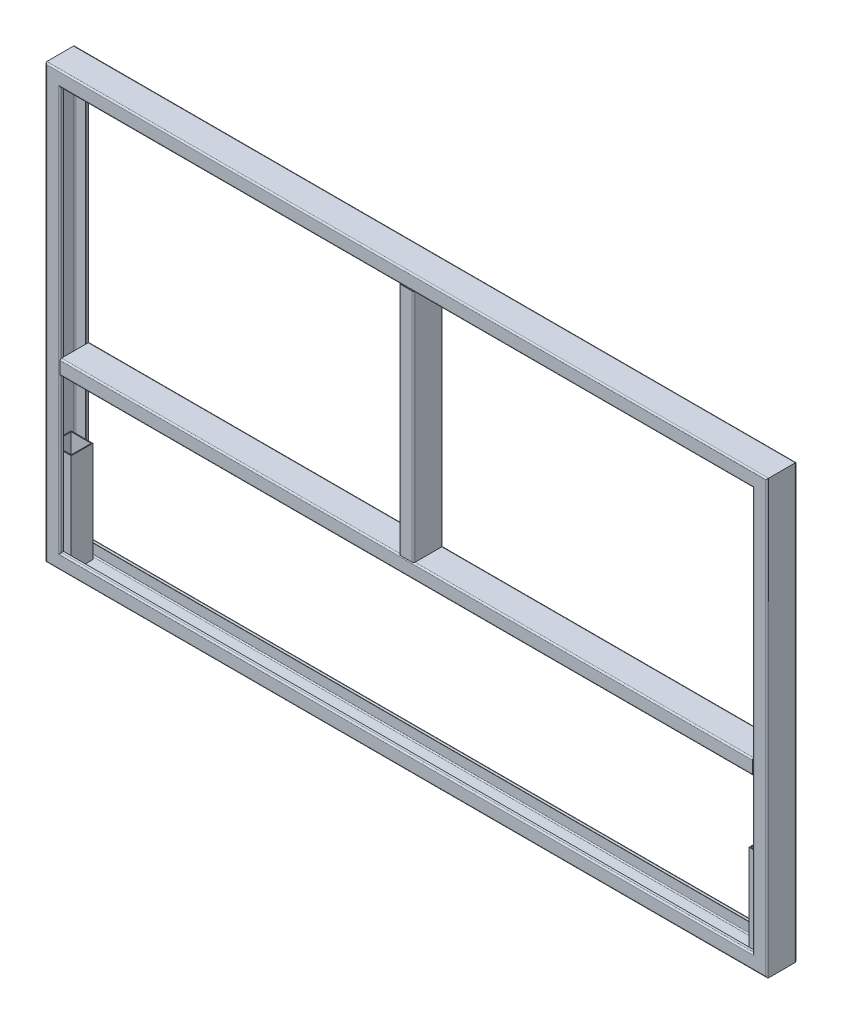
SolidWorks part; units mm, degrees
material "Plain Carbon Steel"
ref_plane "Front Plane" through (0, 0, 0) normal (0, 0, 1) x (1, 0, 0)
ref_plane "Top Plane" through (0, 0, 0) normal (0, 1, 0) x (1, 0, 0)
ref_plane "Right Plane" through (0, 0, 0) normal (1, 0, 0) x (0, 0, -1)
sketch "Sketch1" plane through (0, 0, 0) normal (0, 0, 1) x (1, 0, 0)
  line L0 (0, 750) -> (0, 0) construction
  line L1 (1251, 750) -> (-1251, 750)
  line L2 (1251, 750) -> (1251, -750)
  line L3 (1251, -750) -> (-1251, -750)
  line L4 (-1251, 750) -> (-1251, -750)
  line L5 (-1200, 699) -> (1200, 699)
  line L6 (-1200, 699) -> (-1200, -699)
  line L7 (-1200, -699) -> (1200, -699)
  line L8 (1200, 699) -> (1200, -699)
  line L9 (0, 0) -> (0, -750) construction
  line L10 (-1200, 0) -> (0, 0) construction
  line L11 (0, 0) -> (1200, 0) construction
  dimension "D1" = 2502
  dimension "D2" = 1500
  dimension "D3" = 51
  dimension "D4" = 51
extrude "Boss-Extrude1" add sketch "Sketch1" along normal mid plane 102
fillet "Fillet1" radius 5 16 edges at (1200, 0, -51) (0, -699, -51) (-1200, 0, -51) (0, 699, -51) (0, 750, -51) (-1251, 0, -51) (0, -750, -51) (1251, 0, -51) (0, -699, 51) (1200, 0, 51) (0, 699, 51) (-1200, 0, 51) (0, -750, 51) (-1251, 0, 51) (0, 750, 51) (1251, 0, 51)
shell "Shell1" thickness 12.5 removed face at (1200, 0, 0) removed face at (0, 699, 0) removed face at (-1200, 0, 0) removed face at (0, -699, 0)
shell "Shell2" thickness 1 removed face at (0, -737.5, 0) removed face at (1238.5, 0, 0) removed face at (0, 737.5, 0) removed face at (0, 0, 38.5) removed face at (-1238.5, 0, 0) removed face at (0, 0, -38.5)
sketch "Sketch2" plane through (0, 0, 0) normal (0, 0, 1) x (1, 0, 0)
  line L0 (1200, -699) -> (1200, 699) construction
  line L1 (-1200, -115) -> (1200, -115)
  line L2 (-1200, -115) -> (-1200, -166)
  line L3 (-1200, -166) -> (1200, -166)
  line L4 (1200, -115) -> (1200, -166)
  line L6 (-1200, 699) -> (-1200, -699) construction
  dimension "D1" = 51
  dimension "D2" = 115
extrude "Boss-Extrude2" add sketch "Sketch2" along normal mid plane 102 separate body
fillet "Fillet2" radius 5 4 edges at (0, -115, -51) (0, -166, 51) (0, -115, 51) (0, -166, -51)
shell "Shell3" thickness 12.5 removed face at (0, -166, 0) removed face at (-1200, -140.5, 0) removed face at (1200, -140.5, 0)
shell "Shell4" thickness 1 removed face at (0, -146.75, -38.5) removed face at (0, -127.5, 0) removed face at (0, -146.75, 38.5) removed face at (-1200, -142.5833, 0) removed face at (1200, -142.5833, 0)
sketch "Sketch3" plane through (0, 0, 0) normal (0, 0, -1) x (-1, 0, 0)
  line L0 (0, -166) -> (0, -115) construction
  line L1 (-25.5, 699) -> (25.5, 699)
  line L2 (-25.5, 699) -> (-25.5, -115)
  line L3 (-25.5, -115) -> (25.5, -115)
  line L4 (25.5, 699) -> (25.5, -115)
  line L5 (-1200, -115) -> (1200, -115) construction
  line L7 (1200, 699) -> (-1200, 699) construction
  line L8 (0, -115) -> (0, 0) construction
  line L9 (1200, -166) -> (-1200, -166) construction
  line L10 (-51, -166) -> (51, -166) construction
  line L11 (-51, -166) -> (-51, -699) construction
  line L12 (-51, -699) -> (51, -699) construction
  line L13 (51, -166) -> (51, -699) construction
  line L14 (-1200, -699) -> (1200, -699) construction
  dimension "D1" = 51
  dimension "D2" = 102
extrude "Boss-Extrude3" add sketch "Sketch3" against normal mid plane 102 separate body
sketch "Sketch4" plane through (0, 0, 0) normal (0, 0, 1) x (1, 0, 0)
  line L1 (-51, -166) -> (51, -166)
  line L2 (-51, -166) -> (-51, -699)
  line L3 (-51, -699) -> (51, -699)
  line L4 (51, -166) -> (51, -699)
extrude "Boss-Extrude4" [suppressed] add sketch "Sketch4" against normal blind 51 separate body
fillet "Fillet3" radius 5 4 edges at (25.5, 292, -51) (25.5, 292, 51) (-25.5, 292, 51) (-25.5, 292, -51)
fillet "Fillet4" [suppressed] radius 5
shell "Shell6" thickness 12.5 removed face at (0, 699, 0) removed face at (0, -115, 0) removed face at (-25.5, 292, 0)
shell "Shell7" [suppressed] thickness 12.5
shell "Shell8" thickness 1 removed face at (-2.0833, -115, 0) removed face at (-2.0833, 699, 0) removed face at (-6.25, 292, 38.5) removed face at (13, 292, 0) removed face at (-6.25, 292, -38.5)
shell "Shell9" [suppressed] thickness 1
sketch "Sketch5" plane through (0, -750, 0) normal (0, -1, 0) x (1, 0, 0)
  line L1 (-1250, 37.5) -> (-1175, 37.5)
  line L2 (-1250, 37.5) -> (-1250, -37.5)
  line L3 (-1250, -37.5) -> (-1175, -37.5)
  line L4 (-1175, 37.5) -> (-1175, -37.5)
  line L5 (-1175, 0) -> (0, 0) construction
  dimension "D1" = 75
  dimension "D2" = 1250
extrude "Boss-Extrude5" add sketch "Sketch5" against normal blind 350
sketch "Sketch6" plane through (0, -750, 0) normal (0, -1, 0) x (1, 0, 0)
  line L18 (-1247, 34.5) -> (-1247, -34.5)
  line L19 (-1247, -34.5) -> (-1178, -34.5)
  line L20 (-1178, -34.5) -> (-1178, 34.5)
  line L21 (-1178, 34.5) -> (-1247, 34.5)
  line L22 (-1247, 34.5) -> (-1247, -34.5)
  line L23 (-1247, -34.5) -> (-1178, -34.5)
  line L24 (-1178, -34.5) -> (-1178, 34.5)
  line L25 (-1178, 34.5) -> (-1247, 34.5)
  dimension "D1" = 3
extrude "Cut-Extrude1" cut sketch "Sketch6" against normal blind 350
mirror "Mirror1" about plane through (0, 0, 0) normal (1, 0, 0) of "Cut-Extrude1", "Boss-Extrude5"
